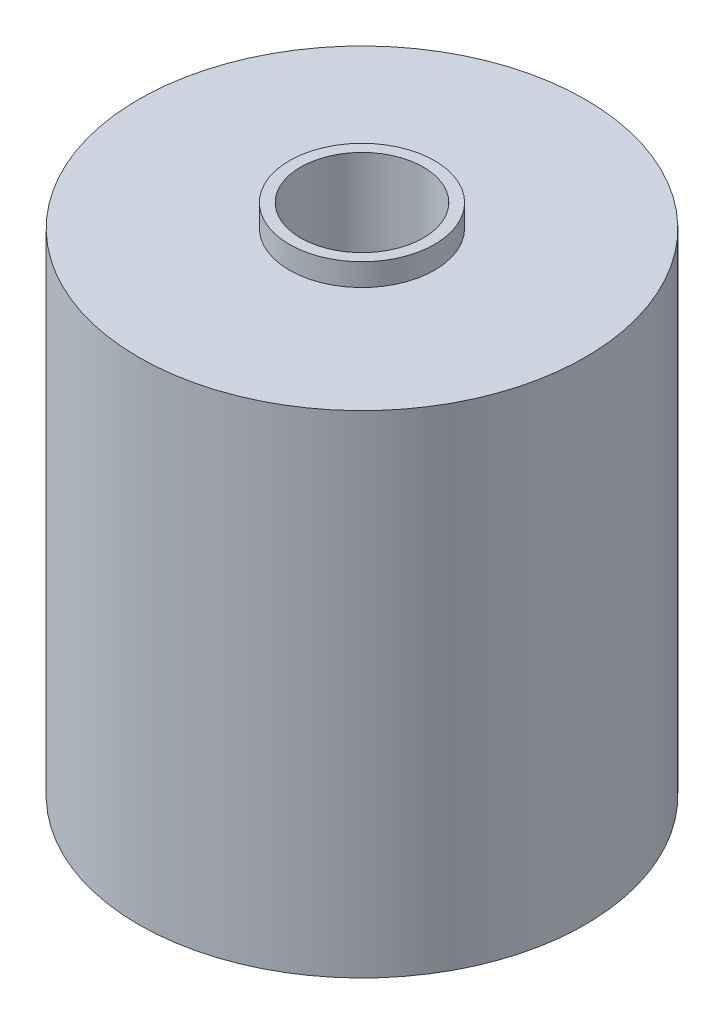
SolidWorks part; units mm, degrees
ref_plane "Plano frontal" through (0, 0, 0) normal (0, 0, 1) x (1, 0, 0)
ref_plane "Plano superior" through (0, 0, 0) normal (0, 1, 0) x (1, 0, 0)
ref_plane "Plano direito" through (0, 0, 0) normal (1, 0, 0) x (0, 0, -1)
sketch "Esboço1" plane through (0, 0, 0) normal (0, 1, 0) x (1, 0, 0)
  circle A0 centre (0, 0) radius 3.25
  circle A1 centre (0, 0) radius 10
  circle A2 centre (0, 0) radius 2.75
  dimension "D1" = 6.5
  dimension "D2" = 20
  dimension "D3" = 5.5
extrude "Ressalto-extrusão1" add sketch "Esboço1" along normal mid plane 22 contours A1 A0 region at (-9.7172, 0, 0)
extrude "Ressalto-extrusão2" add sketch "Esboço1<3>" along normal mid plane 24 contours A0 A2 region at (-3.1581, 0, 0)
sketch "Esboço1<3>" plane through (0, 0, 0) normal (0, 1, 0) x (1, 0, 0) same geometry as "Esboço1"
